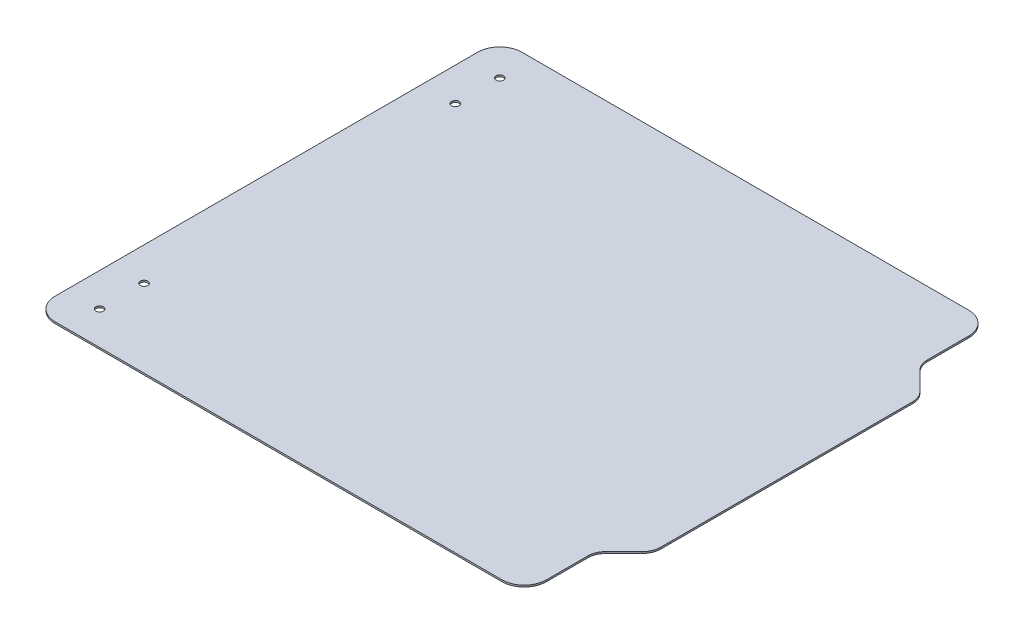
SolidWorks part; units mm, degrees
material "AISI 1020 Steel, Cold Rolled"
ref_plane "Front Plane" through (0, 0, 0) normal (0, 0, 1) x (1, 0, 0)
ref_plane "Top Plane" through (0, 0, 0) normal (0, 1, 0) x (1, 0, 0)
ref_plane "Right Plane" through (0, 0, 0) normal (1, 0, 0) x (0, 0, -1)
sketch "Sketch1" plane through (0, 0, 0) normal (0, 1, 0) x (1, 0, 0)
  line L1 (-117, 105) -> (117, 105)
  line L2 (-117, 105) -> (-117, -105)
  line L3 (-117, -105) -> (117, -105)
  line L4 (117, 105) -> (117, -105)
  line L5 (-117, 105) -> (117, -105) construction
  line L6 (-117, -105) -> (117, 105) construction
  point P0 (0, 0)
  dimension "D1" = 234
  dimension "D2" = 210
extrude "Boss-Extrude1" add sketch "Sketch1" along normal blind 0.76
sketch "Sketch2" plane through (0, 0.76, 0) normal (0, 1, 0) x (1, 0, 0)
  line L0 (117, 60) -> (104, 73)
  line L1 (117, -105) -> (117, 105) construction
  line L2 (104, 73) -> (104, 105)
  line L3 (117, 105) -> (-117, 105) construction
  line L4 (104, 105) -> (117, 105)
  line L5 (117, 105) -> (117, 60)
  line L6 (-0.418, 0) -> (0.418, 0) construction
  line L7 (104, -105) -> (117, -105)
  line L8 (104, -73) -> (104, -105)
  line L9 (117, -60) -> (104, -73)
  line L10 (117, -105) -> (117, -60)
  dimension "D1" = 45
  dimension "D2" = 32
  dimension "D3" = 13
extrude "Cut-Extrude1" cut sketch "Sketch2" against normal blind 0.76
fillet "Fillet1" radius 8 4 edges at (104, 0.38, 73) (117, 0.38, 60) (117, 0.38, -60) (104, 0.38, -73)
fillet "Fillet2" radius 10 4 edges at (-117, 0.38, -105) (-117, 0.38, 105) (104, 0.38, 105) (104, 0.38, -105)
sketch "Sketch3" plane through (0, 0.76, 0) normal (0, 1, 0) x (1, 0, 0)
  circle A0 centre (-102, 70) radius 1.7 construction
  circle A1 centre (-102, 90) radius 1.7 construction
  circle A2 centre (-102, -90) radius 1.7 construction
  circle A3 centre (-102, -70) radius 1.7 construction
  circle A4 centre (-102, 70) radius 1.7
  circle A5 centre (-102, 90) radius 1.7
  circle A6 centre (-102, -90) radius 1.7
  circle A7 centre (-102, -70) radius 1.7
extrude "Cut-Extrude2" cut sketch "Sketch3" against normal through all
